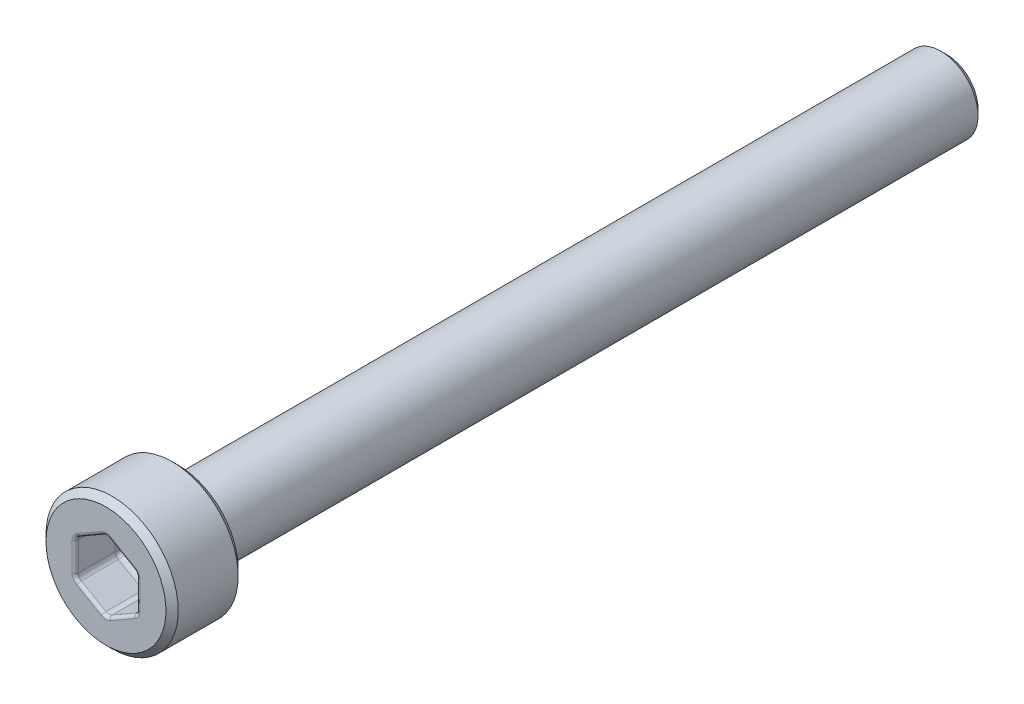
SolidWorks part; units mm, degrees
material "1.4000 (X6Cr13)"
ref_plane "Ebene vorne" through (0, 0, 0) normal (0, 0, 1) x (1, 0, 0)
ref_plane "Ebene oben" through (0, 0, 0) normal (0, 1, 0) x (1, 0, 0)
ref_plane "Ebene rechts" through (0, 0, 0) normal (1, 0, 0) x (0, 0, -1)
sketch "Skizze1" plane through (0, 0, 0) normal (1, 0, 0) x (0, 0, -1)
  line L0 (-21.9199, 0) -> (33.7608, 0) construction
  line L1 (0, 13.9907) -> (0, -9.4798) construction
  line L2 (-2.35, 0) -> (-2.35, 2.15)
  line L3 (-2.35, 2.15) -> (0, 2.15)
  line L4 (0, 2.15) -> (0, 1.21)
  line L5 (0, 1.21) -> (25, 1.21)
  line L6 (25, 1.21) -> (25, 0)
  line L7 (25, 0) -> (-2.35, 0)
  dimension "D1" = 2.42
  dimension "D2" = 2.35
  dimension "D3" = 4.3
  dimension "D4" = 25
revolve "Rotation1" add sketch "Skizze1" angle 360 about L0
sketch "Skizze2" plane through (0, 0, 2.35) normal (0, 0, 1) x (1, 0, 0)
  line L0 (0, 8.6995) -> (0, -7.3778) construction
  line L1 (1, -0.5774) -> (1, 0.5774)
  line L2 (1, 0.5774) -> (0, 1.1547)
  line L3 (0, 1.1547) -> (-1, 0.5774)
  line L4 (-1, 0.5774) -> (-1, -0.5774)
  line L5 (-1, -0.5774) -> (0, -1.1547)
  line L6 (0, -1.1547) -> (1, -0.5774)
  circle A0 centre (0, 0) radius 1 construction
  dimension "D1" = 2
extrude "Schnitt-Linear austragen1" cut sketch "Skizze2" against normal blind 1.5
chamfer "Fase1" distance 0.2 angle 45 3 edges at (2.15, 0, 2.35) (2.15, 0, 0) (1.21, 0, -25)
fillet "Verrundung1" radius 0.2 13 edges at (-0.5, -0.866, 0.85) (-1, 0, 0.85) (-0.5, 0.866, 0.85) (0.5, 0.866, 0.85) (1, 0, 0.85) (0.5, -0.866, 0.85) (-1, -0.5774, 1.6) (0, -1.1547, 1.6) (1, -0.5774, 1.6) (1, 0.5774, 1.6) (0, 1.1547, 1.6) (-1, 0.5774, 1.6) (1.21, 0, 0)
fillet "Verrundung2" radius 0.1 12 edges at (0.9732, -0.5619, 2.35) (0.5, -0.866, 2.35) (0, -1.1238, 2.35) (-0.5, -0.866, 2.35) (-0.9732, -0.5619, 2.35) (-1, 0, 2.35) (-0.9732, 0.5619, 2.35) (-0.5, 0.866, 2.35) (0, 1.1238, 2.35) (0.5, 0.866, 2.35) (0.9732, 0.5619, 2.35) (1, 0, 2.35)
ref_axis "Achse1" through (0, 0, -19.6323) along (0, 0, 1)
